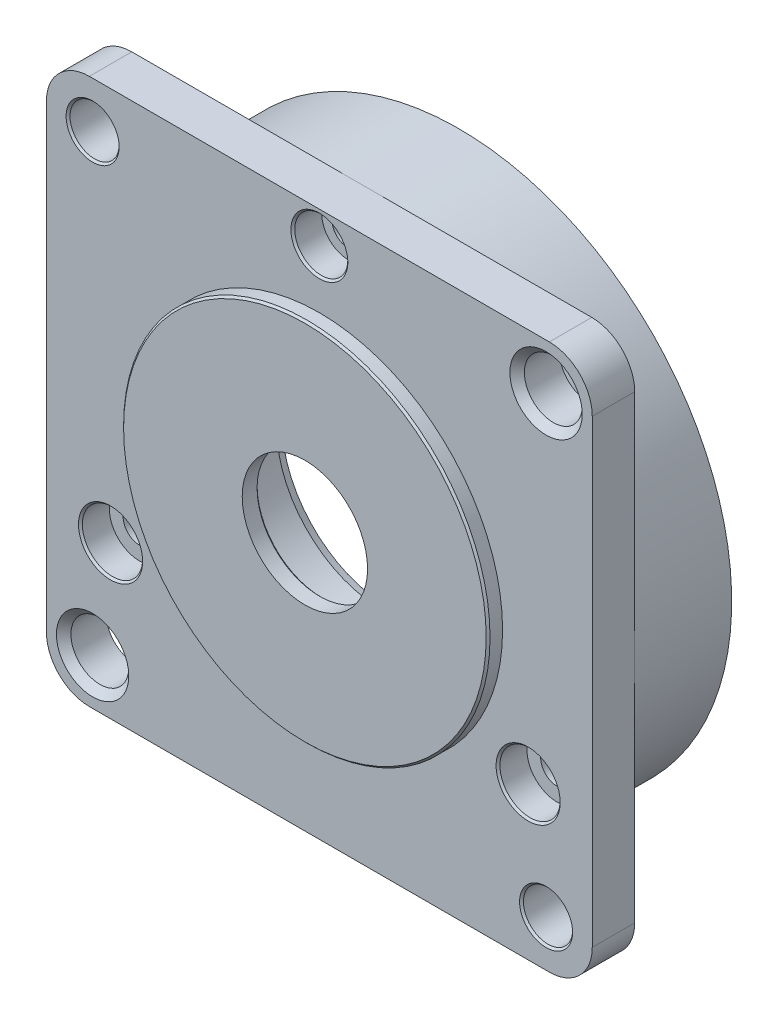
SolidWorks part; units mm, degrees
ref_plane "Ön Düzlem" through (0, 0, 0) normal (0, 0, 1) x (1, 0, 0)
ref_plane "Üst Düzlem" through (0, 0, 0) normal (0, 1, 0) x (1, 0, 0)
ref_plane "Sağ Düzlem" through (0, 0, 0) normal (1, 0, 0) x (0, 0, -1)
sketch "Çizim1" plane through (0, 0, 0) normal (0, 0, 1) x (1, 0, 0)
  line L1 (-23.85, 28.3) -> (23.85, 28.3)
  line L2 (-28.3, 23.85) -> (-28.3, -23.85)
  line L3 (-23.85, -28.3) -> (23.85, -28.3)
  line L4 (28.3, 23.85) -> (28.3, -23.85)
  line L5 (-28.3, 28.3) -> (28.3, -28.3) construction
  line L6 (-28.3, -28.3) -> (28.3, 28.3) construction
  arc A0 (23.85, 28.3) -> (28.3, 23.85) centre (23.85, 23.85) cw
  arc A1 (-23.85, 28.3) -> (-28.3, 23.85) centre (-23.85, 23.85) ccw
  arc A2 (-28.3, -23.85) -> (-23.85, -28.3) centre (-23.85, -23.85) ccw
  arc A3 (23.85, -28.3) -> (28.3, -23.85) centre (23.85, -23.85) ccw
  circle A4 centre (-23.5113, 23.5113) radius 2.55
  circle A5 centre (23.5113, -23.5113) radius 2.55
  circle A6 centre (-23.5113, -23.5113) radius 3
  circle A7 centre (23.5113, 23.5113) radius 3
  circle A8 centre (0, 0) radius 6.5
  circle A9 centre (0, 25) radius 1.7
  circle A10 centre (21.6506, -12.5) radius 1.7
  circle A11 centre (-21.6506, -12.5) radius 1.7
  point P0 (0, 0)
  point P31 (0, 0)
  point P32 (5.4803, -17.9622)
  point P33 (0, 0)
  point P38 (0, 0)
  dimension "D3" = 4.45
  dimension "D4" = 5.1
  dimension "D5" = 5.1
  dimension "D8" = 66.5
  dimension "D10" = 6
  dimension "D11" = 6
  dimension "D12" = 13
  dimension "D13" = 3.4
  dimension "D1" = 56.6
  dimension "D2" = 56.6
  dimension "D6" = 66.5
  dimension "D7" = 33.25
  dimension "D9" = 33.25
  dimension "D14" = 25
  dimension "D15" = 3
extrude "Yükseklik-Ekstrüzyon1" add sketch "Çizim1" along normal blind 4.4
sketch "Çizim2" plane through (0, 0, 4.4) normal (0, 0, 1) x (1, 0, 0)
  circle A0 centre (0, 0) radius 6.5 construction
  circle A1 centre (0, 0) radius 6.5
  circle A2 centre (0, 0) radius 19
  dimension "D1" = 38
extrude "Yükseklik-Ekstrüzyon2" add sketch "Çizim2" along normal blind 1.5
chamfer "Pah1" distance 0.2 angle 45 1 edges at (19, 0, 5.9)
chamfer "Pah2" distance 0.75 angle 45 2 edges at (26.5113, 23.5113, 4.4) (-20.5113, -23.5113, 4.4)
sketch "Çizim3" plane through (0, 0, 4.4) normal (0, 0, 1) x (1, 0, 0)
  circle A0 centre (-21.6506, -12.5) radius 3.125
  circle A1 centre (21.6506, -12.5) radius 3.125
  circle A2 centre (0, 25) radius 2.75
  circle A3 centre (0, 25) radius 1.7 construction
  circle A4 centre (21.6506, -12.5) radius 1.7 construction
  circle A5 centre (-21.6506, -12.5) radius 1.7 construction
  circle A6 centre (0, 25) radius 1.7
  circle A7 centre (21.6506, -12.5) radius 1.7
  circle A8 centre (-21.6506, -12.5) radius 1.7
  dimension "D1" = 6.25
  dimension "D2" = 5.5
extrude "Kes-Ekstrüzyon1" cut sketch "Çizim3" against normal blind 3
chamfer "Pah3" distance 0.2 angle 45 5 edges at (26.0613, -23.5113, 4.4) (-20.9613, 23.5113, 4.4) (2.75, 25, 4.4) (-18.5256, -12.5, 4.4) (24.7756, -12.5, 4.4)
sketch "Çizim4" plane through (0, 0, 0) normal (0, 0, -1) x (-1, 0, 0)
  circle A0 centre (0, 0) radius 11
  dimension "D1" = 22
extrude "Kes-Ekstrüzyon2" cut sketch "Çizim4" against normal blind 3.66
sketch "Çizim5" plane through (0, 0, 3.66) normal (0, 0, -1) x (-1, 0, 0)
  circle A0 centre (0, 0) radius 8.9
  dimension "D1" = 17.8
extrude "Kes-Ekstrüzyon3" cut sketch "Çizim5" against normal blind 0.5
chamfer "Pah4" distance 0.2 angle 45 1 edges at (-6.5, 0, 4.16)
sketch "Çizim6" plane through (0, 0, 0) normal (0, 0, -1) x (-1, 0, 0)
  circle A0 centre (0, 0) radius 12.75
  circle A1 centre (0, 0) radius 11 construction
  circle A2 centre (0, 0) radius 11
  dimension "D1" = 25.5
extrude "Yükseklik-Ekstrüzyon3" add sketch "Çizim6" along normal blind 2.9
chamfer "Pah5" distance 0.2 angle 75 1 edges at (-11, 0, -2.9) first distance on face at (-12.75, 0, -2.9)
sketch "Çizim7" plane through (0, 0, 0) normal (0, 0, -1) x (-1, 0, 0)
  circle A0 centre (0, 0) radius 26.75
  circle A1 centre (0, 0) radius 28.3
  dimension "D1" = 53.5
  dimension "D2" = 56.6
extrude "Yükseklik-Ekstrüzyon4" add sketch "Çizim7" along normal blind 10.06
sketch "Çizim8" plane through (0, 0, 0) normal (0, 0, -1) x (-1, 0, 0)
  line L0 (-2.9, 25) -> (-2.9, 26.5923)
  line L1 (2.9, 25) -> (2.9, 26.5923)
  line L2 (23.1006, -9.9885) -> (24.4796, -10.7847)
  line L3 (20.2006, -15.0115) -> (21.5796, -15.8076)
  line L4 (-20.2006, -15.0115) -> (-21.5796, -15.8076)
  line L5 (-23.1006, -9.9885) -> (-24.4796, -10.7847)
  circle A0 centre (0, 0) radius 12.75 construction
  circle A1 centre (0, 0) radius 26.75 construction
  circle A2 centre (0, 0) radius 12.75
  arc A3 (-2.9, 26.5923) -> (-24.4796, -10.7847) centre (0, 0) ccw
  arc A4 (-2.9, 25) -> (2.9, 25) centre (0, 25) ccw
  arc A6 (23.1006, -9.9885) -> (20.2006, -15.0115) centre (21.6506, -12.5) ccw
  arc A7 (-20.2006, -15.0115) -> (-23.1006, -9.9885) centre (-21.6506, -12.5) ccw
  arc A8 (-21.5796, -15.8076) -> (21.5796, -15.8076) centre (0, 0) ccw
  arc A9 (24.4796, -10.7847) -> (2.9, 26.5923) centre (0, 0) ccw
  point P11 (-21.9864, -8.0859)
  point P12 (0, 0)
  point P13 (0, 0)
  point P24 (0, 0)
  dimension "D1" = 5.8
  dimension "D2" = 3
extrude "Kes-Ekstrüzyon4" cut sketch "Çizim8" against normal blind 0.5
sketch "Çizim10" plane through (0, 0, -10.06) normal (0, 0, -1) x (-1, 0, 0)
  circle A0 centre (0, 0) radius 27.5
  dimension "D1" = 55
extrude "Kes-Ekstrüzyon5" cut sketch "Çizim10" against normal blind 1.5
